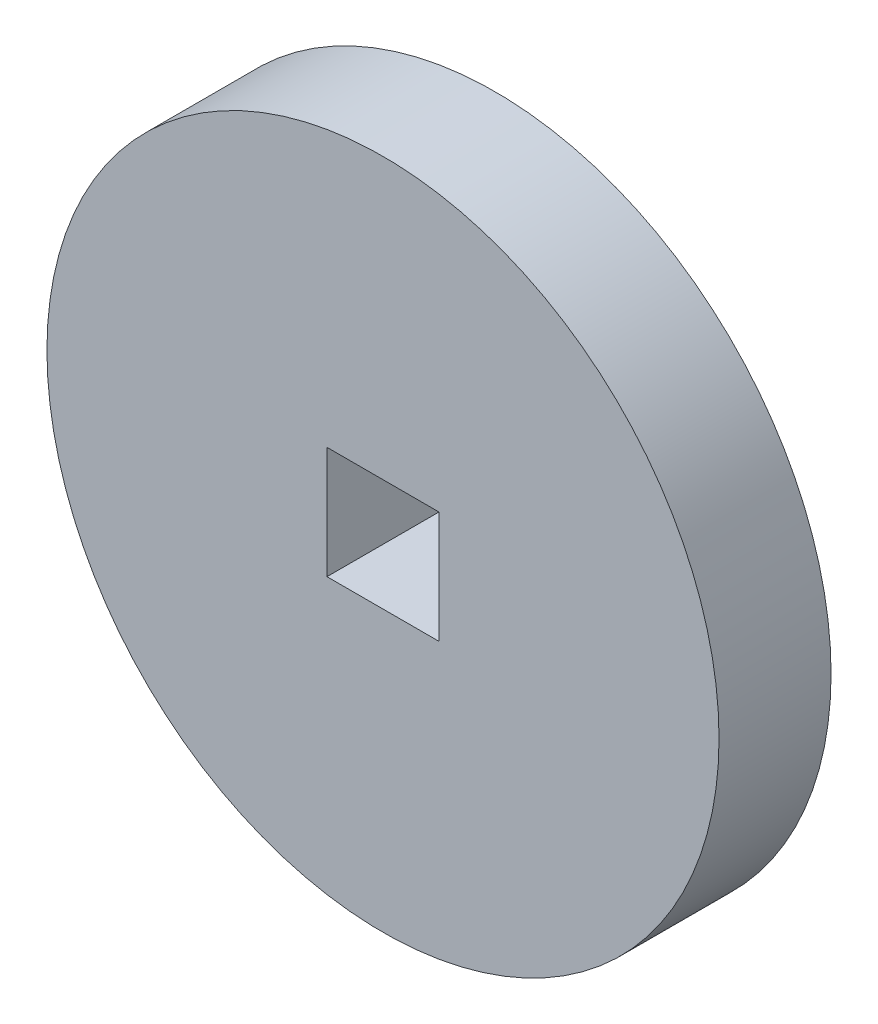
SolidWorks part; units mm, degrees
ref_plane "Front Plane" through (0, 0, 0) normal (0, 0, 1) x (1, 0, 0)
ref_plane "Top Plane" through (0, 0, 0) normal (0, 1, 0) x (1, 0, 0)
ref_plane "Right Plane" through (0, 0, 0) normal (1, 0, 0) x (0, 0, -1)
sketch "Sketch1" plane through (0, 0, 0) normal (0, 0, 1) x (1, 0, 0)
  circle A0 centre (0, 0) radius 30
  dimension "D1" = 60
extrude "Boss-Extrude1" add sketch "Sketch1" against normal blind 10
sketch "Sketch2" plane through (0, 0, 0) normal (0, 0, 1) x (1, 0, 0)
  line L1 (-5, 5) -> (5, 5)
  line L2 (-5, 5) -> (-5, -5)
  line L3 (-5, -5) -> (5, -5)
  line L4 (5, 5) -> (5, -5)
  line L5 (-5, 5) -> (5, -5) construction
  line L6 (-5, -5) -> (5, 5) construction
  point P0 (0, 0)
  dimension "D1" = 10
extrude "Cut-Extrude2" cut sketch "Sketch2" against normal through all
ref_axis "Axis1" through (0, 0, -10) along (0, 0, 1)
